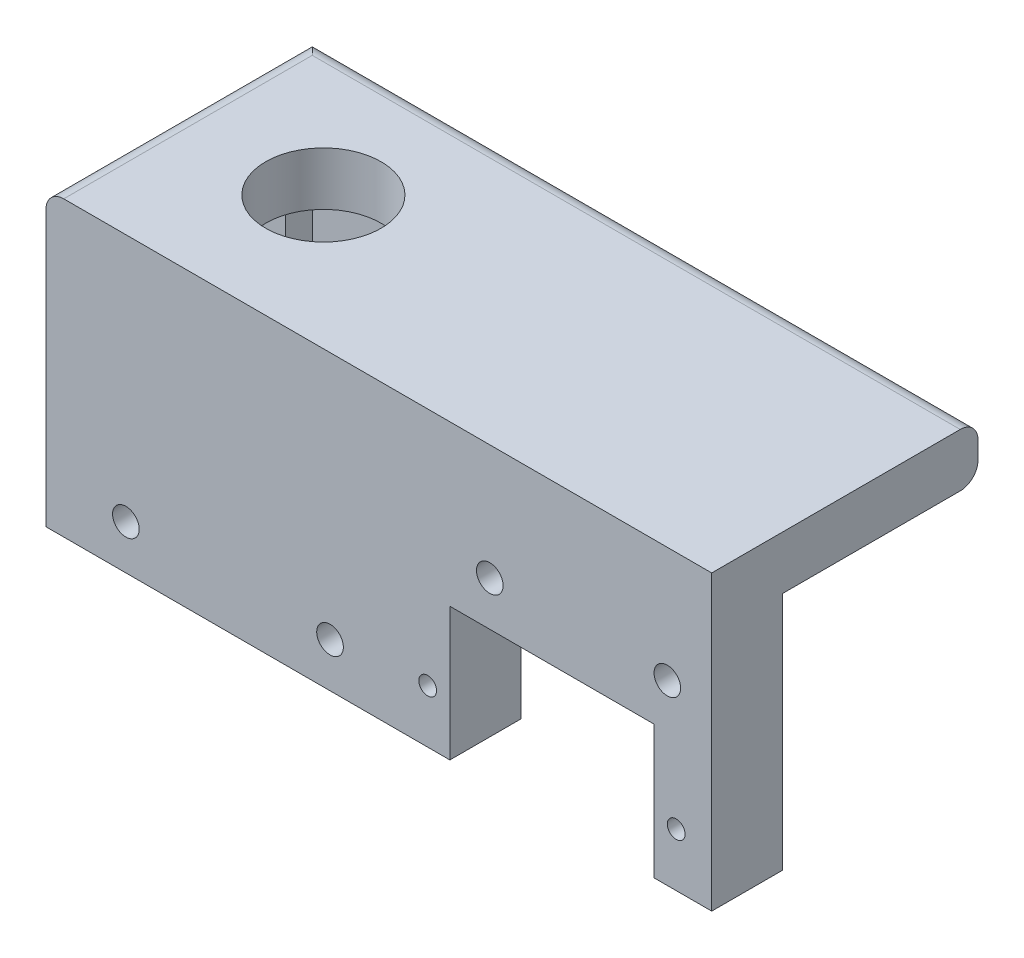
SolidWorks part; units mm, degrees
ref_plane "Front Plane" through (0, 0, 0) normal (0, 0, 1) x (1, 0, 0)
ref_plane "Top Plane" through (0, 0, 0) normal (0, 1, 0) x (1, 0, 0)
ref_plane "Right Plane" through (0, 0, 0) normal (1, 0, 0) x (0, 0, -1)
sketch "Sketch1" plane through (0, -4.342, 0) normal (0, -1, 0) x (1, 0, 0)
  line L0 (-40.9843, 28.2004) -> (-18.4843, 28.2004) construction
  line L1 (-11.5696, 28.2004) -> (-86.5696, 28.2004)
  line L2 (-11.5696, 28.2004) -> (-11.5696, -1.7996)
  line L3 (-11.5696, -1.7996) -> (-86.5696, -1.7996)
  line L4 (-86.5696, 28.2004) -> (-86.5696, -1.7996)
  dimension "D1" = 75
  dimension "D2" = 30
extrude "Boss-Extrude1" add sketch "Sketch1" along normal blind 6 contours L1 L4 L3 L2
sketch "Sketch2" plane through (0, -10.342, 0) normal (0, -1, 0) x (-1, 0, 0)
  line L1 (86.5696, 1.7996) -> (38.5696, 1.7996)
  line L2 (86.5696, 1.7996) -> (86.5696, -2.7004)
  line L3 (86.5696, -2.7004) -> (38.5696, -2.7004)
  line L4 (38.5696, 1.7996) -> (38.5696, -2.7004)
  line L5 (38.5696, 1.7996) -> (43.5696, 1.7996)
  line L6 (38.5696, 1.7996) -> (38.5696, -7.2004)
  line L7 (38.5696, -7.2004) -> (43.5696, -7.2004)
  line L8 (43.5696, 1.7996) -> (43.5696, -7.2004)
  line L9 (11.5696, -28.2004) -> (86.5696, -28.2004) construction
  line L10 (86.5696, 1.7996) -> (82.0696, 1.7996)
  line L11 (86.5696, 1.7996) -> (86.5696, -28.2004)
  line L12 (86.5696, -28.2004) -> (82.0696, -28.2004)
  line L13 (82.0696, 1.7996) -> (82.0696, -28.2004)
  line L14 (11.5696, -28.2004) -> (11.5696, 1.7996) construction
  line L15 (86.5696, -28.2004) -> (41.0696, -28.2004)
  line L16 (86.5696, -28.2004) -> (86.5696, -23.7004)
  line L17 (86.5696, -23.7004) -> (41.0696, -23.7004)
  line L18 (41.0696, -28.2004) -> (41.0696, -23.7004)
  line L19 (46.0696, -28.2004) -> (41.0696, -28.2004)
  line L20 (46.0696, -28.2004) -> (46.0696, -20.2004)
  line L21 (46.0696, -20.2004) -> (41.0696, -20.2004)
  line L22 (41.0696, -28.2004) -> (41.0696, -20.2004)
  line L24 (11.5696, -28.2004) -> (18.0696, -28.2004)
  line L25 (11.5696, -28.2004) -> (11.5696, -20.2004)
  line L26 (11.5696, -20.2004) -> (18.0696, -20.2004)
  line L27 (18.0696, -28.2004) -> (18.0696, -20.2004)
  dimension "D1" = 4.5
  dimension "D2" = 48
  dimension "D3" = 5
  dimension "D4" = 9
  dimension "D5" = 4.5
  dimension "D6" = 4.5
  dimension "D7" = 0
  dimension "D8" = 29.5
  dimension "D9" = 40.5
  dimension "D10" = 0
  dimension "D11" = 8
  dimension "D12" = 6.5
extrude "Boss-Extrude4" add sketch "Sketch2" along normal blind 27 contours L16 L15 L18 L17 | L2 L1 L4 L3 | L11 L10 L13 L12 | L6 L5 L8 L7 | L20 L19 L22 L21 | L25 L24 L27 L26
sketch "Sketch7" plane through (-38.5696, 0, 0) normal (1, 0, 0) x (0, 0, -1)
  line L1 (-7.2004, -37.342) -> (-2.7004, -37.342)
  line L2 (-7.2004, -37.342) -> (-7.2004, -22.342)
  line L3 (-7.2004, -22.342) -> (-2.7004, -22.342)
  line L4 (-2.7004, -37.342) -> (-2.7004, -22.342)
  dimension "D1" = 15
  dimension "D2" = 4.5
extrude "Cut-Extrude1" cut sketch "Sketch7" against normal blind 6
sketch "Sketch9" plane through (0, -4.342, 0) normal (0, 1, 0) x (1, 0, 0)
  line L1 (-86.5696, -28.2004) -> (-86.5696, 1.7996) construction
  line L2 (-11.5696, 1.7996) -> (-86.5696, 1.7996) construction
  circle A0 centre (-70.3196, -13.2004) radius 6.5
  dimension "D1" = 16.25
  dimension "D2" = 15
  dimension "D3" = 13
extrude "Cut-Extrude2" cut sketch "Sketch9" against normal blind 30
sketch "Sketch10" plane through (0, 0, 28.2004) normal (0, 0, 1) x (1, 0, 0)
  line L0 (-86.5696, -37.342) -> (-86.5696, -4.342) construction
  line L2 (-86.5696, -37.342) -> (-41.0696, -37.342) construction
  circle A0 centre (-77.5696, -32.342) radius 1.5
  dimension "D1" = 9
  dimension "D2" = 3
  dimension "D3" = 5
extrude "Cut-Extrude3" cut sketch "Sketch10" against normal blind 50
sketch "Sketch11" plane through (0, 0, 28.2004) normal (0, 0, 1) x (1, 0, 0)
  line L0 (-86.5696, -37.342) -> (-86.5696, -4.342) construction
  circle A0 centre (-54.5696, -32.342) radius 1.5
  circle A1 centre (-77.5696, -32.342) radius 1.5 construction
  dimension "D1" = 32
  dimension "D2" = 3
  dimension "D3" = 0
extrude "Cut-Extrude4" cut sketch "Sketch11" against normal blind 10
sketch "Sketch12" plane through (-86.5696, 0, 0) normal (-1, 0, 0) x (0, 0, 1)
  line L0 (-1.7996, -37.342) -> (28.2004, -37.342) construction
  line L1 (5.7004, -37.342) -> (20.7004, -37.342)
  line L2 (5.7004, -37.342) -> (5.7004, -11.342)
  line L3 (5.7004, -11.342) -> (20.7004, -11.342)
  line L4 (20.7004, -37.342) -> (20.7004, -11.342)
  line L5 (28.2004, -4.342) -> (-1.7996, -4.342) construction
  point P8 (13.2004, -4.342)
  dimension "D1" = 15
  dimension "D2" = 7.5
  dimension "D3" = 26
extrude "Cut-Extrude5" cut sketch "Sketch12" against normal blind 5
sketch "Sketch14" plane through (-41.0696, 0, 0) normal (1, 0, 0) x (0, 0, -1)
  line L0 (-20.2004, -37.342) -> (-20.2004, -10.342) construction
  line L1 (-20.2004, -22.342) -> (-28.2004, -22.342)
  line L2 (-20.2004, -22.342) -> (-20.2004, -10.342)
  line L3 (-20.2004, -10.342) -> (-28.2004, -10.342)
  line L4 (-28.2004, -22.342) -> (-28.2004, -10.342)
  dimension "D1" = 12
  dimension "D2" = 0
extrude "Boss-Extrude6" add sketch "Sketch14" along normal up to vertex (23 mm away) up to point (-18.0696, -10.342, 28.2004)
sketch "Sketch15" plane through (0, 0, 28.2004) normal (0, 0, 1) x (1, 0, 0)
  line L0 (-11.5696, -37.342) -> (-18.0696, -37.342) construction
  line L2 (-41.0696, -37.342) -> (-41.0696, -22.342) construction
  line L3 (-18.0696, -37.342) -> (-18.0696, -22.342) construction
  circle A0 centre (-15.5696, -31.342) radius 1
  circle A1 centre (-43.5696, -31.342) radius 1
  dimension "D1" = 2
  dimension "D2" = 6
  dimension "D3" = 2.5
  dimension "D4" = 0
  dimension "D5" = 2.5
  dimension "D6" = 2
extrude "Cut-Extrude6" cut sketch "Sketch15" against normal blind 11
sketch "Sketch16" plane through (0, 0, 20.2004) normal (0, 0, -1) x (-1, 0, 0)
  line L1 (11.5696, -37.342) -> (11.5696, -10.342) construction
  line L2 (18.0696, -22.342) -> (41.0696, -22.342) construction
  circle A0 centre (36.5696, -17.342) radius 1.5
  circle A1 centre (16.5696, -17.342) radius 1.5
  dimension "D1" = 3
  dimension "D2" = 3
  dimension "D3" = 5
  dimension "D4" = 5
  dimension "D5" = 5
  dimension "D6" = 20
extrude "Cut-Extrude7" cut sketch "Sketch16" against normal blind 11
fillet "Fillet1" radius 2 4 edges at (-86.5696, -4.342, 13.2004) (-25.0696, -10.342, -1.7996) (-49.0696, -4.342, -1.7996) (-38.5696, -23.842, -1.7996)
fillet "Fillet2" radius 1 3 edges at (-86.5696, -11.342, 13.2004) (-86.5696, -24.342, 5.7004) (-86.5696, -24.342, 20.7004)
